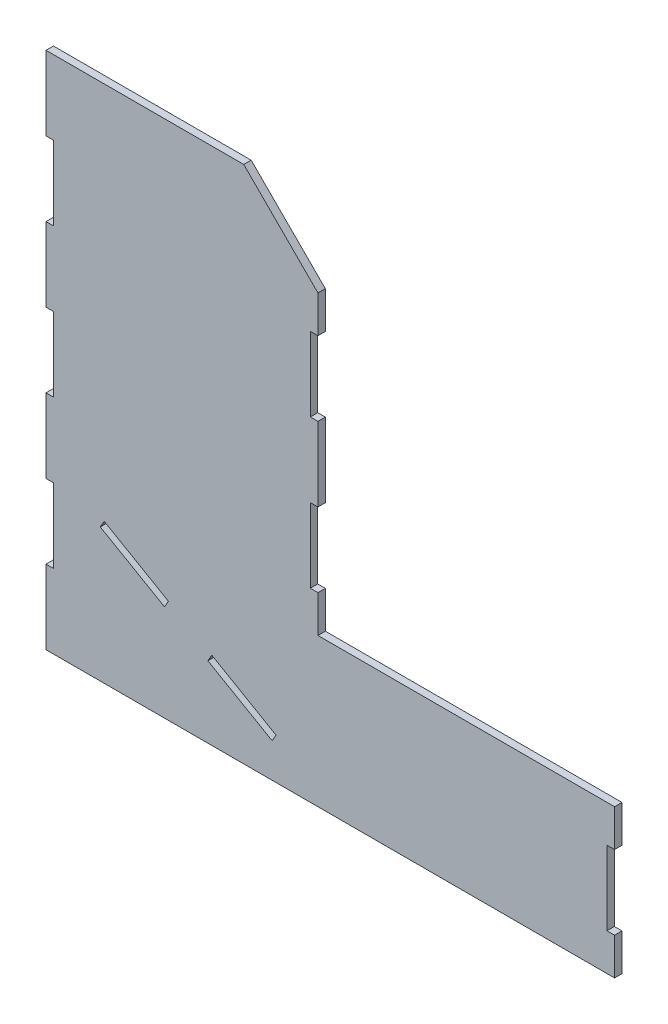
SolidWorks part; units mm, degrees
material "Maple"
ref_plane "Front Plane" through (0, 0, 0) normal (0, 0, 1) x (1, 0, 0)
ref_plane "Top Plane" through (0, 0, 0) normal (0, 1, 0) x (1, 0, 0)
ref_plane "Right Plane" through (0, 0, 0) normal (1, 0, 0) x (0, 0, -1)
sketch "Sketch1" plane through (0, 0, 0) normal (0, 0, 1) x (1, 0, 0)
  line L0 (-93.9149, 144.3977) -> (-93.9149, -65.6023)
  line L1 (-93.9149, -65.6023) -> (136.0851, -65.6023)
  line L2 (136.0851, -65.6023) -> (136.0851, -5.6023)
  line L3 (136.0851, -5.6023) -> (16.0851, -5.6023)
  line L4 (16.0851, -5.6023) -> (16.0851, 114.3977)
  line L5 (16.0851, 114.3977) -> (-13.9149, 144.3977)
  line L6 (-13.9149, 144.3977) -> (-93.9149, 144.3977)
  line L7 (-92.4149, 144.3977) -> (-92.4149, -65.6023) construction
  line L8 (-92.4149, 114.3977) -> (-92.4149, 84.3977)
  line L9 (-93.9149, 39.3977) -> (16.0851, 39.3977) construction
  line L10 (-92.4149, 24.3977) -> (-92.4149, 54.3977)
  line L11 (-92.4149, -35.6023) -> (-92.4149, -5.6023)
  line L12 (136.0851, -35.6023) -> (-93.9149, -35.6023) construction
  line L13 (14.5851, 114.3977) -> (14.5851, -5.6023) construction
  line L14 (14.5851, 99.3977) -> (14.5851, 69.3977)
  line L15 (14.5851, 54.3977) -> (0.09, 54.3977) construction
  line L16 (14.5851, 9.3977) -> (14.5851, 39.3977)
  line L17 (134.5851, -5.6023) -> (134.5851, -65.6023) construction
  line L18 (134.5851, -20.6023) -> (134.5851, -50.6023)
  line L19 (-88.9149, 0.0195) -> (16.0851, -60.6023) construction
  line L20 (-71.1728, -10.2239) -> (-45.1921, -25.2239)
  line L21 (-36.4149, -30.2914) -> (-32.7388, -23.9243) construction
  line L22 (-1.657, -50.3589) -> (-27.6377, -35.3589)
  point P19 (-92.4149, 39.3977)
  dimension "D1" = 210
  dimension "D2" = 230
  dimension "D3" = 110
  dimension "D5" = 60
  dimension "D6" = 30
  dimension "D4" = 45
  dimension "D7" = 1.5
  dimension "D8" = 0
  dimension "D9" = 0
  dimension "D10" = 30
  dimension "D11" = 30
  dimension "D12" = 30
  dimension "D13" = 30
  dimension "D14" = 30
  dimension "D15" = 1.5
  dimension "D16" = 0
  dimension "D17" = 0
  dimension "D18" = 30
  dimension "D19" = 30
  dimension "D20" = 1.5
  dimension "D21" = 0
  dimension "D22" = 0
  dimension "D23" = 30
  dimension "D24" = 30
  dimension "D25" = 3.5
  dimension "D26" = 5
  dimension "D27" = 30
extrude "Boss-Extrude1" add sketch "Sketch1" along normal mid plane 3 contours L5 L6 L0 L1 L2 L3 L4 region at (-11.8546, 19.8751, 0)
extrude "Cut-Extrude-Thin1" cut sketch "Sketch1<3>" against normal through all both and the other way through all thin contours L8 | L10 | L11 | L14 | L16 | L18 | L20 | L22 thin type mid plane wall 3.18
sketch "Sketch1<3>" plane through (0, 0, 0) normal (0, 0, 1) x (1, 0, 0) same geometry as "Sketch1"
fillet "Fillet2" [suppressed] radius 4
equation "\"D7@Sketch1\"= \"lateral offset@tower.Assembly\""
equation "\"D8@Sketch1\" = \"vertical offset@tower.Assembly\""
equation "\"D9@Sketch1\"= \"vertical offset@tower.Assembly\""
equation "\"D12@Sketch1\"=\"D10@Sketch1\""
equation "\"D13@Sketch1\"=\"D10@Sketch1\""
equation "\"D11@Sketch1\"=\"D10@Sketch1\""
equation "\"D14@Sketch1\"=\"D10@Sketch1\""
equation "\"D1@Boss-Extrude1\" = \"T@tower.Assembly\""
equation "\"D15@Sketch1\"=\"D7@Sketch1\""
equation "\"D16@Sketch1\"=\"D8@Sketch1\""
equation "\"D17@Sketch1\"=\"D8@Sketch1\""
equation "\"D18@Sketch1\"=\"D10@Sketch1\""
equation "\"D19@Sketch1\"=\"D18@Sketch1\""
equation "\"D20@Sketch1\"=\"D7@Sketch1\""
equation "\"D21@Sketch1\"=\"D8@Sketch1\""
equation "\"D22@Sketch1\"=\"D8@Sketch1\""
equation "\"D23@Sketch1\"=\"D10@Sketch1\""
equation "\"D25@Sketch1\"=(\"T@tower.Assembly\"/2)+2"
equation "\"D26@Sketch1\"=\"T@tower.Assembly\"+2"
equation "\"D27@Sketch1\"=\"D10@Sketch1\""
